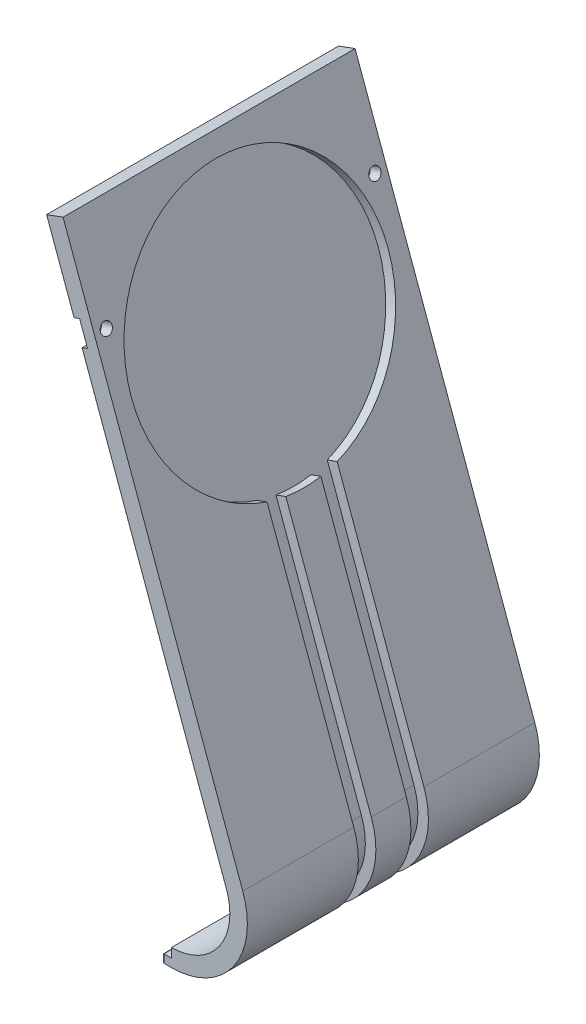
SolidWorks part; units mm, degrees
material "PLA"
ref_plane "前视基准面" through (0, 0, 0) normal (0, 0, 1) x (1, 0, 0)
ref_plane "上视基准面" through (0, 0, 0) normal (0, 1, 0) x (1, 0, 0)
ref_plane "右视基准面" through (0, 0, 0) normal (1, 0, 0) x (0, 0, -1)
other "Configuration Table"
sketch "草图2" plane through (0, 0, 0) normal (0, 0, 1) x (1, 0, 0)
  line L0 (38.2711, 17.4699) -> (5.8755, 106.4762) construction
  line L5 (38.2711, 17.4699) -> (7.4967, 102.022)
  line L10 (28.8742, 4.0497) -> (28.8742, 3.0497) construction
  line L11 (6.4731, 107.7579) -> (8.8224, 108.6129) construction
  arc A0 (28.8742, 4.0497) -> (38.2711, 17.4699) centre (28.8742, 14.0497) ccw
  arc A1 (28.8742, 4.0497) -> (38.2711, 17.4699) centre (28.8742, 14.0497) ccw construction
  dimension "D2" = 10
  dimension "D1" = 5.74
extrude "整体拉伸-薄壁1" add sketch "草图2" along normal mid plane 50 thin thin type one direction wall 3
sketch "草图4" plane through (42.228, 15.3697, 0) normal (0.9397, 0.342, 0) x (0, 0, -1)
  line L0 (-25, 93.3054) -> (25, 93.3054) construction
  circle A0 centre (0, 67.9054) radius 22
  dimension "D1" = 44
  dimension "D2" = 25.4
extrude "中间圆切除-拉伸1" cut sketch "草图4" against normal blind 1.8
sketch "草图3" plane through (0, 0, 0) normal (0, 0, 1) x (1, 0, 0)
  line L0 (41.0902, 18.4959) -> (10.3157, 103.0481) construction
  line L1 (41.0902, 18.4959) -> (10.3157, 103.0481) construction
  line L2 (28.8742, 1.0497) -> (28.8742, 4.0497) construction
  line L5 (39.3988, 17.8803) -> (24.836, 57.891)
  line L6 (39.3988, 17.8803) -> (8.6243, 102.4325) construction
  line L7 (28.8742, 2.8497) -> (28.8742, 2.8497) construction
  line L9 (24.836, 57.891) -> (26.5275, 58.5067) construction
  line L16 (24.836, 57.891) -> (23.81, 60.7101)
  line L17 (27.0769, 2.9492) -> (17.4206, 7.9003) construction
  arc A0 (28.8742, 4.0497) -> (38.2711, 17.4699) centre (28.8742, 14.0497) ccw construction
  arc A1 (17.4206, 7.9003) -> (41.0902, 18.4959) centre (28.8742, 14.0497) ccw construction
  arc A2 (28.8742, 2.8497) -> (39.3988, 17.8803) centre (28.8742, 14.0497) ccw
  dimension "D2" = 3
  dimension "D1" = 1.8
extrude "线槽切除-拉伸-薄壁1" cut sketch "草图3" against normal blind 3 from offset 6 thin thin type one direction wall 1.8
mirror "镜向1" about plane through (0, 0, 0) normal (0, 0, 1) of "线槽切除-拉伸-薄壁1"
sketch "草图11" plane through (28.8742, 0, 0) normal (-1, 0, 0) x (0, 0, 1)
  line L0 (-25, 1.0497) -> (-25, 4.0497) construction
  line L1 (-25, 2.4497) -> (-6.1, 2.4497)
  line L2 (-25, 2.4497) -> (-25, 1.0497)
  line L3 (-25, 1.0497) -> (-6.1, 1.0497)
  line L4 (-6.1, 2.4497) -> (-6.1, 1.0497)
  line L5 (25, 1.0497) -> (6, 1.0497) construction
  line L6 (6.1, 2.4497) -> (25, 2.4497)
  line L7 (6.1, 2.4497) -> (6.1, 1.0497)
  line L8 (6.1, 1.0497) -> (25, 1.0497)
  line L9 (25, 2.4497) -> (25, 1.0497)
  line L11 (-6, 1.0497) -> (-6, 2.8497) construction
  line L13 (6, 1.0497) -> (6, 2.8497) construction
  line L14 (25, 4.0497) -> (-25, 4.0497) construction
  dimension "D1" = 1.6
  dimension "D2" = 0.1
  dimension "D3" = 0.1
  dimension "D4" = 1.6
extrude "底部卡扣凸台-拉伸3" add sketch "草图11" along normal blind 1.5
fillet "底部卡扣圆角1" radius 0.25 8 edges at (27.3742, 2.4497, 15.55) (27.3742, 1.7497, 25) (27.3742, 1.0497, 15.55) (27.3742, 1.7497, 6.1) (27.3742, 2.4497, -15.55) (27.3742, 1.7497, -6.1) (27.3742, 1.0497, -15.55) (27.3742, 1.7497, -25)
sketch "草图12" plane through (39.409, 14.3437, 0) normal (-0.9397, -0.342, 0) x (0, 0, 1)
  line L0 (-36.5, 79.5431) -> (36.5, 79.5431) construction
  line L2 (-25, 3.3268) -> (-25, 93.3054) construction
  line L3 (25, 3.3268) -> (25, 93.3054) construction
  circle A0 centre (23, 77.5431) radius 1
  circle A1 centre (-23, 77.5431) radius 1
  dimension "D1" = 2
  dimension "D2" = 2
  dimension "D3" = 2
  dimension "D4" = 2
  dimension "D5" = 2
  dimension "D6" = 2
extrude "螺丝孔" cut sketch "草图12" against normal through all
sketch "草图13" plane through (39.409, 14.3437, 0) normal (-0.9397, -0.342, 0) x (0, 0, 1)
  line L0 (25, 3.3268) -> (25, 93.3054) construction
  line L1 (23, 79.5431) -> (25, 79.5431)
  line L3 (23, 75.5431) -> (25, 75.5431)
  line L4 (25, 79.5431) -> (25, 75.5431)
  line L5 (-36.5, 79.5431) -> (36.5, 79.5431) construction
  line L6 (0, 93.3054) -> (0, 78.3622) construction
  line L7 (25, 93.3054) -> (-25, 93.3054) construction
  line L8 (-25, 79.5431) -> (-25, 75.5431)
  line L9 (-23, 75.5431) -> (-25, 75.5431)
  line L10 (-23, 79.5431) -> (-25, 79.5431)
  arc A0 (23, 79.5431) -> (23, 75.5431) centre (23, 77.5431) ccw
  arc A1 (-23, 79.5431) -> (-23, 75.5431) centre (-23, 77.5431) cw
  dimension "D1" = 4
extrude "切除-拉伸1" cut sketch "草图13" against normal blind 1
